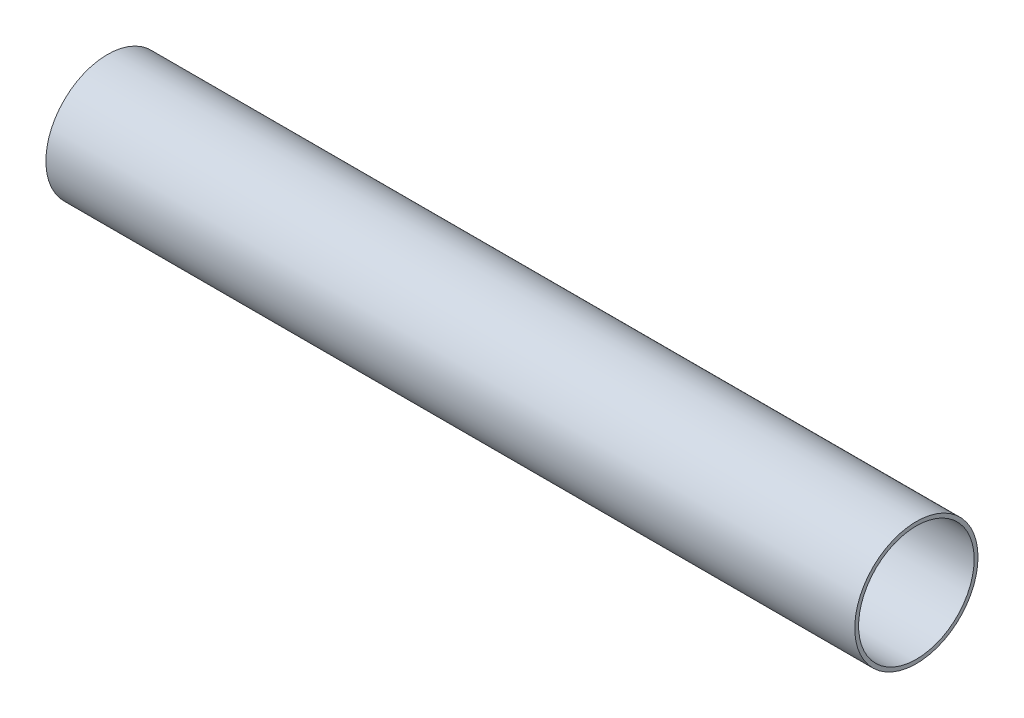
SolidWorks part; units mm, degrees
other "Exploded View1" [suppressed]
material "PC High Viscosity"
ref_plane "Front Plane" through (0, 0, 0) normal (0, 0, 1) x (1, 0, 0)
ref_plane "Top Plane" through (0, 0, 0) normal (0, 1, 0) x (1, 0, 0)
ref_plane "Right Plane" through (0, 0, 0) normal (1, 0, 0) x (0, 0, -1)
sketch "Sketch1" plane through (0, 0, 0) normal (1, 0, 0) x (0, 0, -1)
  circle A0 centre (0, 0) radius 25.4
  dimension "D1" = 50.8
extrude "Extrude-Thin1" add sketch "Sketch1" along normal mid plane 333.375 thin thin type one direction reverse wall 1.5875
sketch "Sketch2" plane through (0, 0, 0) normal (0, 0, 1) x (1, 0, 0)
  line L0 (-166.6875, -25.4) -> (166.6875, -25.4) construction
  line L1 (111.4135, -25.4) -> (132.4135, -25.4)
  line L2 (111.4135, -25.4) -> (111.4135, 25.4)
  line L3 (111.4135, 25.4) -> (132.4135, 25.4)
  line L4 (132.4135, -25.4) -> (132.4135, 25.4)
  line L5 (166.6875, 25.4) -> (-166.6875, 25.4) construction
  line L6 (166.6875, -25.4) -> (166.6875, 25.4) construction
  line L7 (0, 0) -> (0, 11.1276) construction
  line L8 (-132.4135, -25.4) -> (-132.4135, 25.4)
  line L9 (-111.4135, 25.4) -> (-132.4135, 25.4)
  line L10 (-111.4135, -25.4) -> (-111.4135, 25.4)
  line L11 (-111.4135, -25.4) -> (-132.4135, -25.4)
  dimension "D1" = 34.274
  dimension "D2" = 21
equation "\"D2@Sketch2\"=21mm"
